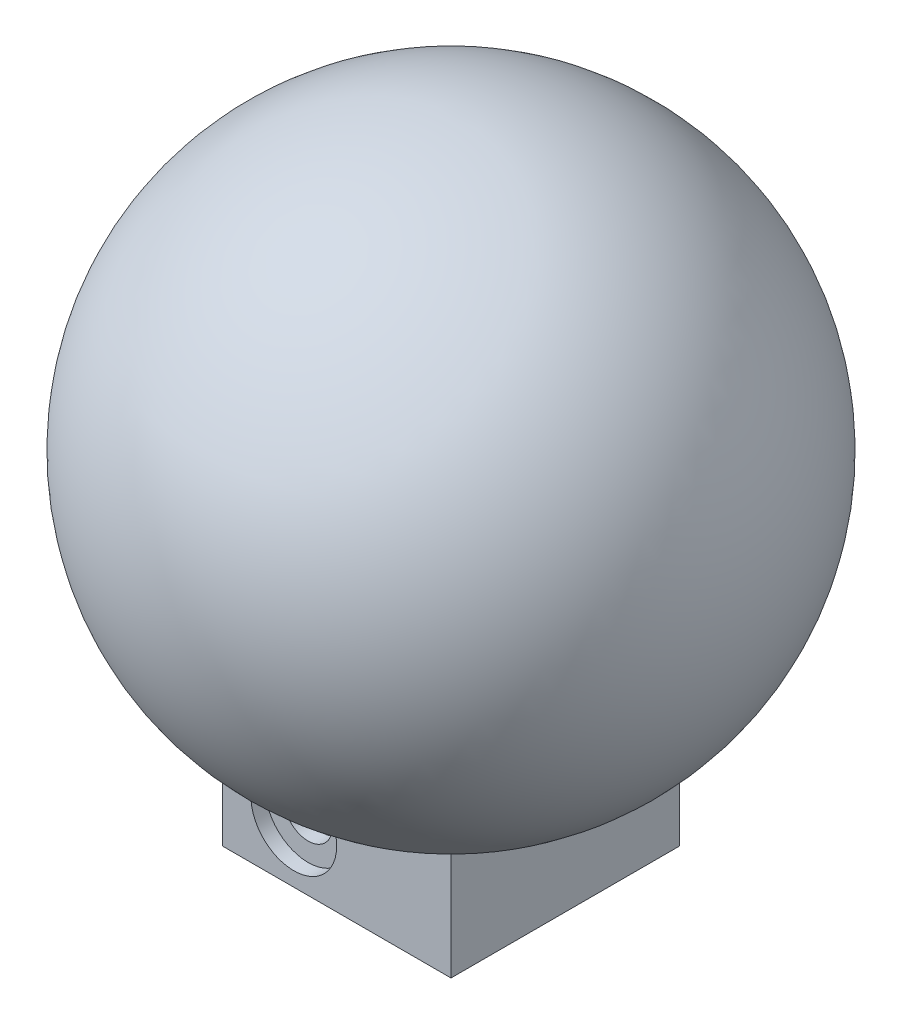
SolidWorks part; units mm, degrees
ref_plane "Front Plane" through (0, 0, 0) normal (0, 0, 1) x (1, 0, 0)
ref_plane "Top Plane" through (0, 0, 0) normal (0, 1, 0) x (1, 0, 0)
ref_plane "Right Plane" through (0, 0, 0) normal (1, 0, 0) x (0, 0, -1)
sketch "Sketch1" plane through (0, 0, 0) normal (0, 0, 1) x (1, 0, 0)
  line L0 (0, 0) -> (0, 40)
  arc A0 (0, 40) -> (0, 0) centre (0, 20) cw
  dimension "D1" = 20
revolve "Revolve1" add sketch "Sketch1" angle 360 about L0
sketch "Sketch2" plane through (0, 0, 0) normal (0, 1, 0) x (1, 0, 0)
  line L0 (6, 6) -> (-6, 6)
  line L1 (8, 8) -> (-8, 8)
  line L2 (8, 8) -> (8, -8)
  line L3 (8, -8) -> (-8, -8)
  line L4 (-8, 8) -> (-8, -8)
  line L5 (8, 8) -> (-8, -8) construction
  line L6 (8, -8) -> (-8, 8) construction
  line L7 (-6, 6) -> (-6, -6)
  line L8 (6, -6) -> (-6, -6)
  line L9 (6, 6) -> (6, -6)
  point P0 (0, 0)
  dimension "D1" = 16
  dimension "D2" = 2
extrude "Boss-Extrude1" add sketch "Sketch2" along normal up to surface and the other way blind 4
sketch "Sketch3" plane through (0, -4, 0) normal (0, -1, 0) x (1, 0, 0)
  line L4 (6, 6) -> (-6, 6)
  line L5 (-6, 6) -> (-6, -6)
  line L6 (-6, -6) -> (6, -6)
  line L7 (6, -6) -> (6, 6)
  line L8 (6, 6) -> (-6, 6)
  line L9 (-6, 6) -> (-6, -6)
  line L10 (-6, -6) -> (6, -6)
  line L11 (6, -6) -> (6, 6)
  dimension "D1" = 0
extrude "Cut-Extrude1" cut sketch "Sketch3" against normal blind 10
sketch "Sketch4" plane through (0, 0, 6) normal (0, 0, -1) x (-1, 0, 0)
  line L0 (-6, -4) -> (-6, 6) construction
  line L1 (6, -4) -> (6, 6) construction
  line L2 (-6, -4) -> (-6, 6) construction
  line L3 (6, -4) -> (6, 6) construction
  line L4 (0, 0) -> (6, 0) construction
  line L7 (-8, -4) -> (8, -4) construction
  circle A0 centre (3, 0) radius 1.7
  circle A1 centre (3, 0) radius 3 construction
  dimension "D1" = 3.4
  dimension "D3" = 6
  dimension "D2" = 4
  dimension "D4" = 3
extrude "Cut-Extrude2" cut sketch "Sketch4" against normal blind 3
sketch "Sketch5" plane through (0, 0, -6) normal (0, 0, 1) x (1, 0, 0)
  line L0 (6, -4) -> (6, 6) construction
  line L1 (-6, -4) -> (-6, 6) construction
  line L2 (6, -4) -> (6, 6) construction
  line L3 (-6, -4) -> (-6, 6) construction
  line L4 (8, -4) -> (-8, -4) construction
  circle A0 centre (3, 0) radius 1.7
  dimension "D2" = 3.4
  dimension "D1" = 4
  dimension "D3" = 3
extrude "Cut-Extrude3" cut sketch "Sketch5" against normal blind 3
sketch "Sketch6" plane through (0, 0, -8) normal (0, 0, -1) x (-1, 0, 0)
  circle A0 centre (-3, 0) radius 3
  dimension "D1" = 6
extrude "Cut-Extrude4" cut sketch "Sketch6" against normal blind 1 and the other way through all
sketch "Sketch7" plane through (0, 0, 8) normal (0, 0, 1) x (1, 0, 0)
  circle A0 centre (-3, 0) radius 3
  dimension "D1" = 6
extrude "Cut-Extrude5" cut sketch "Sketch7" against normal blind 1 and the other way through all
